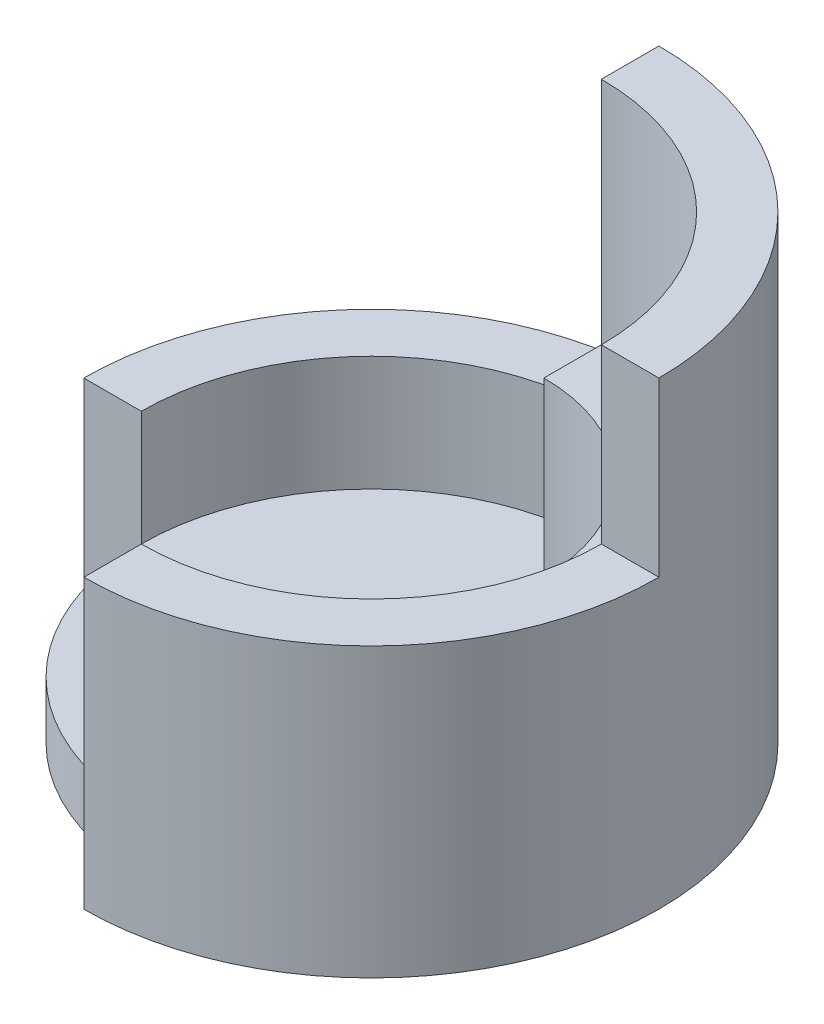
SolidWorks part; units mm, degrees
ref_plane "Front Plane" through (0, 0, 0) normal (0, 0, 1) x (1, 0, 0)
ref_plane "Top Plane" through (0, 0, 0) normal (0, 1, 0) x (1, 0, 0)
ref_plane "Right Plane" through (0, 0, 0) normal (1, 0, 0) x (0, 0, -1)
sketch "Sketch1" plane through (0, 0, 0) normal (0, 1, 0) x (1, 0, 0)
  line L0 (0, 5) -> (0, 4)
  line L1 (-5, 0) -> (-4, 0)
  line L2 (0, -4) -> (0, -5)
  circle A0 centre (0, 0) radius 1
  circle A1 centre (0, 0) radius 4
  arc A2 (0, 4) -> (-4, 0) centre (0, 0) ccw
  arc A3 (0, 5) -> (-5, 0) centre (0, 0) ccw
  arc A4 (0, 5) -> (0, -5) centre (0, 0) cw
  arc A5 (0, 4) -> (0, -4) centre (0, 0) cw
  dimension "D1" = 2
  dimension "D2" = 8
  dimension "D3" = 1
  dimension "D4" = 1
extrude "Boss-Extrude1" add sketch "Sketch1" along normal blind 1 contours A1 A0 | A4 L0 A1 L2 | L0 A3 L1 A1 region at (4.8882, 0, 0) region at (-2.8766, 0, -2.8766) region at (2.7484, 0, -2.7484)
sketch "Sketch2" plane through (0, 1, 0) normal (0, 1, 0) x (1, 0, 0)
  line L0 (0, 3) -> (0, 5)
  line L1 (0, -3) -> (0, -5)
  arc A0 (0, 5) -> (0, -5) centre (0, 0) cw
  arc A1 (0, -5) -> (-5, 0) centre (0, 0) ccw construction
  arc A2 (0, 3) -> (0, -3) centre (0, 0) cw
  dimension "D1" = 2
extrude "Boss-Extrude2" add sketch "Sketch2" along normal blind 4
sketch "Sketch4" plane through (0, 5, 0) normal (0, 1, 0) x (1, 0, 0)
  line L0 (0, -3) -> (0, -5) construction
  line L1 (0, 5) -> (0, 3) construction
  line L2 (0, 5) -> (0, 4)
  line L3 (0, -4) -> (0, -5)
  arc A0 (0, 5) -> (0, -5) centre (0, 0) cw
  arc A1 (0, -4) -> (0, 4) centre (-0.1178, 0) ccw
  dimension "D2" = 4.0017
  dimension "D3" = 5
  dimension "D1" = 1
extrude "Boss-Extrude3" add sketch "Sketch4" along normal blind 3
sketch "Sketch6" plane through (0, 0, 0) normal (-1, 0, 0) x (0, 0, 1)
  line L0 (4, 5) -> (-4, 5) construction
  line L1 (0, 5) -> (5, 5)
  line L2 (0, 5) -> (0, 8)
  line L3 (0, 8) -> (5, 8)
  line L4 (5, 5) -> (5, 8)
extrude "Cut-Extrude1" cut sketch "Sketch6" against normal blind 6
sketch "Sketch7" plane through (0, 5, 0) normal (0, 1, 0) x (1, 0, 0)
  circle A0 centre (0, 0) radius 4
  arc A1 (-4, 0) -> (0, -4) centre (0, 0) ccw construction
extrude "Cut-Extrude2" cut sketch "Sketch7" against normal blind 1 and the other way blind 3
sketch "Sketch8" plane through (0, 1, 0) normal (0, 1, 0) x (1, 0, 0)
  line L0 (0, 5) -> (0, 4)
  line L1 (-5, 0) -> (-4, 0)
  arc A0 (0, 4) -> (-4, 0) centre (0, 0) ccw
  arc A1 (0, 5) -> (-5, 0) centre (0, 0) ccw
extrude "Boss-Extrude4" add sketch "Sketch8" along normal blind 2
